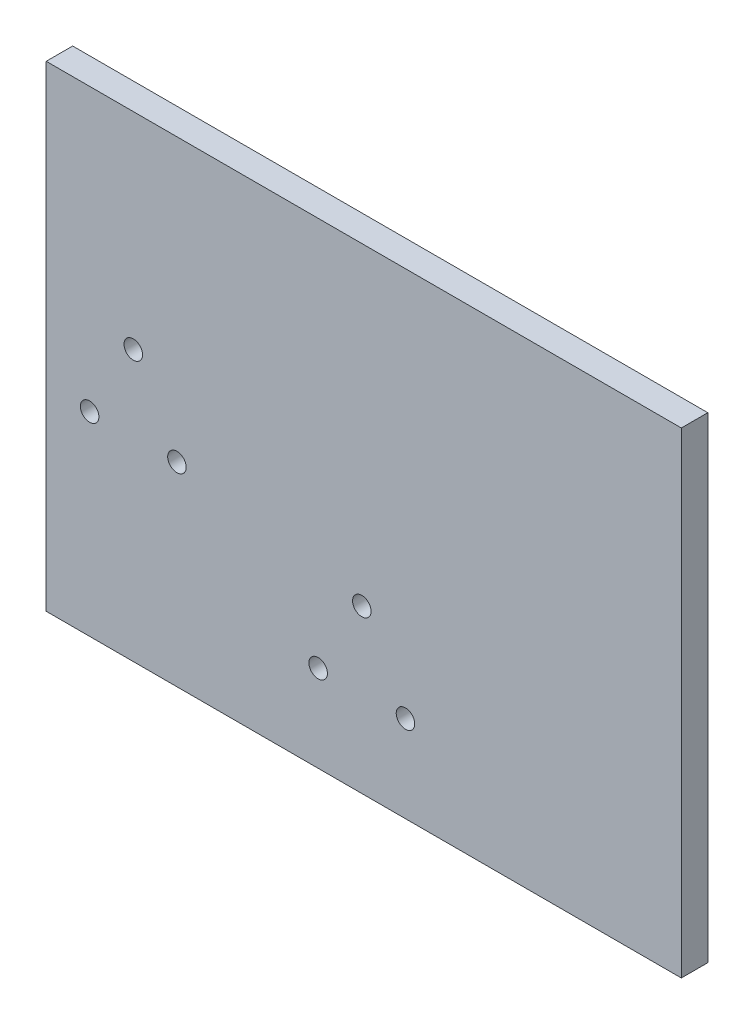
SolidWorks part; units mm, degrees
ref_plane "前视基准面" through (0, 0, 0) normal (0, 0, 1) x (1, 0, 0)
ref_plane "上视基准面" through (0, 0, 0) normal (0, 1, 0) x (1, 0, 0)
ref_plane "右视基准面" through (0, 0, 0) normal (1, 0, 0) x (0, 0, -1)
other "Configuration Table"
sketch "草图1" plane through (0, 0, 0) normal (0, 0, 1) x (1, 0, 0)
  line L1 (60, -45) -> (-60, -45)
  line L2 (60, -45) -> (60, 45)
  line L3 (60, 45) -> (-60, 45)
  line L4 (-60, -45) -> (-60, 45)
  line L5 (60, -45) -> (-60, 45) construction
  line L6 (60, 45) -> (-60, -45) construction
  point P0 (0, 0)
  dimension "D1" = 120
  dimension "D2" = 90
extrude "凸台-拉伸1" add sketch "草图1" along normal blind 5
sketch "草图2" plane through (0, 0, 0) normal (0, 0, -1) x (-1, 0, 0)
  circle A0 centre (0.3679, -23.85) radius 9.525
  circle A1 centre (43.5504, -3.4579) radius 9.525
  dimension "D1" = 19.05
  dimension "D2" = 19.05
sketch "草图3" plane through (0, 0, 0) normal (0, 0, -1) x (-1, 0, 0)
  circle A0 centre (43.5504, 6.0671) radius 1.75
  circle A1 centre (43.5504, -3.4579) radius 9.525 construction
  circle A2 centre (0.3679, -14.325) radius 1.75
  circle A3 centre (0.3679, -23.85) radius 9.525 construction
  circle A4 centre (51.7993, -8.2204) radius 1.75
  circle A5 centre (35.3015, -8.2204) radius 1.75
  circle A6 centre (8.6168, -28.6125) radius 1.75
  circle A7 centre (-7.8809, -28.6125) radius 1.75
  point P14 (43.5504, -3.4579)
  point P19 (0.3679, -23.85)
  dimension "D1" = 3.5
  dimension "D2" = 3.5
  dimension "D3" = 3
  dimension "D4" = 3
extrude "切除-拉伸1" cut sketch "草图3" against normal blind 10
